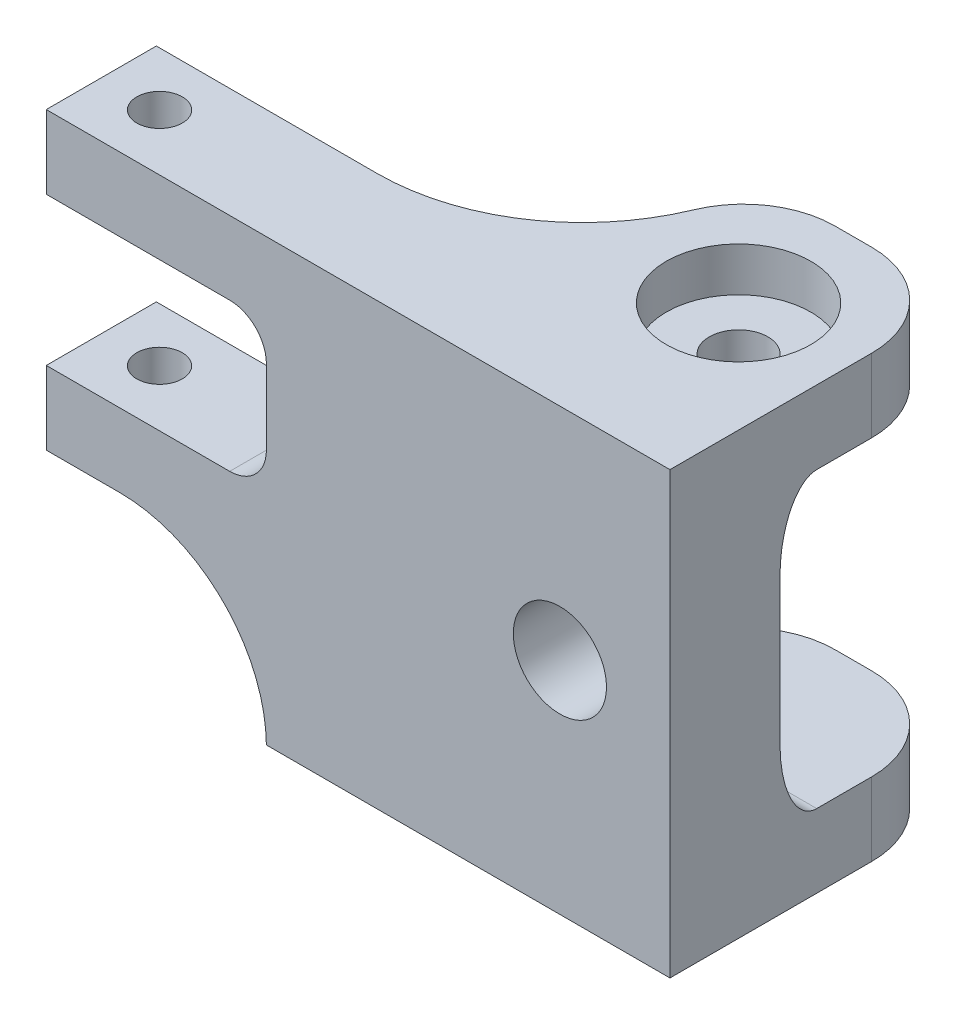
SolidWorks part; units mm, degrees
material "Copper"
ref_plane "Front Plane" through (0, 0, 0) normal (0, 0, 1) x (1, 0, 0)
ref_plane "Top Plane" through (0, 0, 0) normal (0, 1, 0) x (1, 0, 0)
ref_plane "Right Plane" through (0, 0, 0) normal (1, 0, 0) x (0, 0, -1)
sketch "Sketch1" plane through (0, 0, 0) normal (0, 0, 1) x (1, 0, 0)
  line L1 (-15, -30) -> (15, -30)
  line L2 (-15, -30) -> (-15, 30)
  line L3 (-15, 30) -> (15, 30)
  line L4 (15, -30) -> (15, 30)
  line L5 (-15, -30) -> (15, 30) construction
  line L6 (-15, 30) -> (15, -30) construction
  line L7 (-15, 30) -> (-70, 30)
  line L8 (-15, 30) -> (-15, -30)
  line L9 (-15, -30) -> (-70, -30)
  line L10 (-70, 30) -> (-70, -30)
  line L11 (-70, 20) -> (-40, 20)
  line L12 (-70, 20) -> (-70, -0.2)
  line L13 (-70, -0.2) -> (-40, -0.2)
  line L14 (-40, 20) -> (-40, -0.2)
  line L15 (-70, -30) -> (-40, -30)
  line L16 (-70, -30) -> (-70, -10.2)
  line L17 (-70, -10.2) -> (-40, -10.2)
  line L18 (-40, -30) -> (-40, -10.2)
  circle A0 centre (0, 0) radius 6.35
  point P0 (0, 0)
  dimension "D1" = 12.7
  dimension "D2" = 30
  dimension "D3" = 60
  dimension "D4" = 55
  dimension "D5" = 10
  dimension "D6" = 20.2
  dimension "D7" = 30
  dimension "D8" = 10
extrude "Boss-Extrude1" add sketch "Sketch1" along normal blind 15 contours L11 L14 L13 L10 L9 L2 L7 | L1 L4 L3 L2 A0 region at (-14.3292, 0, 0) region at (-35.3571, 2.8286, 0)
sketch "Sketch2" plane through (0, 0, 0) normal (0, 0, -1) x (-1, 0, 0)
  line L1 (-15, 30) -> (15, 30)
  line L2 (-15, 30) -> (-15, 20)
  line L3 (-15, 20) -> (15, 20)
  line L4 (15, 30) -> (15, 20)
  line L5 (-15, -30) -> (15, -30)
  line L6 (-15, -30) -> (-15, -20)
  line L7 (-15, -20) -> (15, -20)
  line L8 (15, -30) -> (15, -20)
  dimension "D1" = 30
  dimension "D2" = 10
extrude "Boss-Extrude2" add sketch "Sketch2" along normal blind 25
fillet "Fillet1" radius 12.5 4 edges at (15, 25, -25) (15, -25, -25) (-15, 25, -25) (-15, -25, -25)
sketch "Sketch5" plane through (0, 30, 0) normal (0, 1, 0) x (1, 0, 0)
  line L0 (-2.5, 25) -> (2.5, 25) construction
  circle A0 centre (0, 9.35) radius 4
  dimension "D1" = 8
  dimension "D2" = 15.65
extrude "Cut-Extrude1" cut sketch "Sketch5" against normal through all
sketch "Sketch6" plane through (0, 30, 0) normal (0, 1, 0) x (1, 0, 0)
  circle A0 centre (0, 9.35) radius 9.85
  dimension "D1" = 19.7
extrude "Cut-Extrude2" cut sketch "Sketch6" against normal blind 6
sketch "Sketch7" plane through (0, -30, 0) normal (0, -1, 0) x (1, 0, 0)
  circle A0 centre (0, -9.35) radius 9.85
  dimension "D1" = 19.7
extrude "Cut-Extrude3" cut sketch "Sketch7" against normal blind 6
fillet "Fillet2" radius 10 2 edges at (0, -20, 0) (0, 20, 0) second distance 5 first distance on face at (6.35, 0, 0)
sketch "Sketch9" plane through (0, 30, 0) normal (0, 1, 0) x (1, 0, 0)
  line L0 (0, 9.35) -> (0, -7.3261) construction
  line L1 (0, -7.3261) -> (-62.2361, -7.3261) construction
  line L2 (-62.2361, -7.3261) -> (0, 9.35) construction
  circle A0 centre (-62.2361, -7.3261) radius 3.1
  dimension "D2" = 6.2
  dimension "D1" = 15
  dimension "D3" = 62.2361
fillet "Fillet3" radius 28 2 edges
extrude "Cut-Extrude4" cut sketch "Sketch9" against normal through all
fillet "Fillet4" radius 20 1 edges at (-40, -10.2, 7.5)
fillet "Fillet5" radius 5 2 edges at (-40, -0.2, 7.5) (-40, 20, 7.5)
